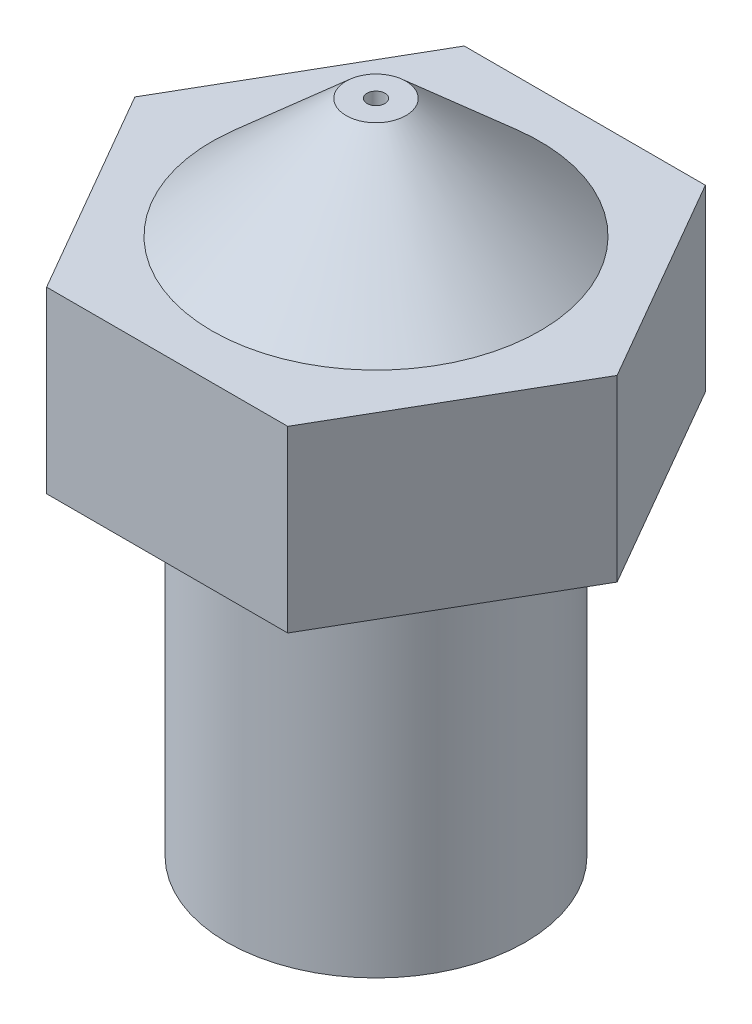
SolidWorks part; units mm, degrees
material "Copper"
ref_plane "Front Plane" through (0, 0, 0) normal (0, 0, 1) x (1, 0, 0)
ref_plane "Top Plane" through (0, 0, 0) normal (0, 1, 0) x (1, 0, 0)
ref_plane "Right Plane" through (0, 0, 0) normal (1, 0, 0) x (0, 0, -1)
sketch "Sketch1" plane through (0, 0, 0) normal (0, 1, 0) x (1, 0, 0)
  line L1 (4.0415, 0) -> (2.0207, 3.5)
  line L2 (2.0207, 3.5) -> (-2.0207, 3.5)
  line L3 (-2.0207, 3.5) -> (-4.0415, 0)
  line L4 (-4.0415, 0) -> (-2.0207, -3.5)
  line L5 (-2.0207, -3.5) -> (2.0207, -3.5)
  line L6 (2.0207, -3.5) -> (4.0415, 0)
  circle A0 centre (0, 0) radius 3.5 construction
  dimension "D1" = 7
extrude "Boss-Extrude1" add sketch "Sketch1" along normal blind 3
sketch "Sketch2" plane through (0, 3, 0) normal (0, 1, 0) x (1, 0, 0)
  circle A0 centre (0, 0) radius 2.75
  dimension "D1" = 5.5
extrude "Boss-Extrude2" add sketch "Sketch2" along normal blind 2 draft 48.36
sketch "Sketch4" plane through (0, 5, 0) normal (0, 1, 0) x (1, 0, 0)
  circle A0 centre (0, 0) radius 0.15
  dimension "D1" = 0.3
extrude "Cut-Extrude1" cut sketch "Sketch4" against normal blind 1.5
sketch "Sketch6" plane through (0, 0, 0) normal (0, -1, 0) x (1, 0, 0)
  circle A0 centre (0, 0) radius 2.5
  dimension "D1" = 5
extrude "Boss-Extrude3" add sketch "Sketch6" along normal blind 6
sketch "Sketch7" plane through (0, -6, 0) normal (0, -1, 0) x (1, 0, 0)
  circle A0 centre (0, 0) radius 1
  dimension "D1" = 2
extrude "Cut-Extrude3" cut sketch "Sketch7" against normal up to surface (9.5 mm away) up to face at (0, 3.5, 0.15)
